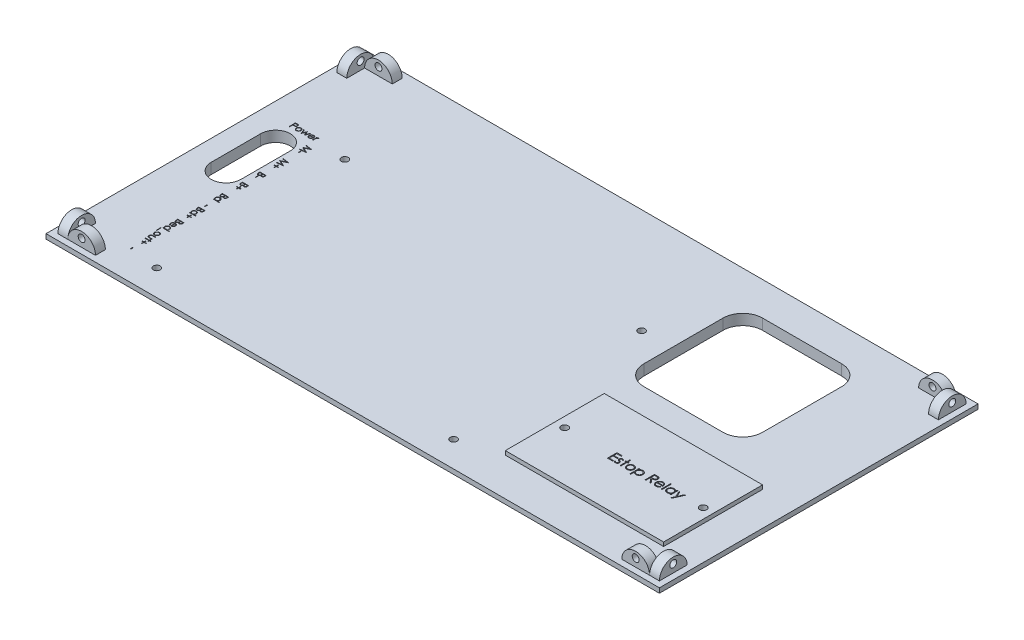
SolidWorks part; units mm, degrees
ref_plane "Front Plane" through (0, 0, 0) normal (0, 0, 1) x (1, 0, 0)
ref_plane "Top Plane" through (0, 0, 0) normal (0, 1, 0) x (1, 0, 0)
ref_plane "Right Plane" through (0, 0, 0) normal (1, 0, 0) x (0, 0, -1)
sketch "Sketch1" plane through (0, 0, 0) normal (0, 1, 0) x (1, 0, 0)
  line L1 (-111.0644, -68.8857) -> (48.9356, -68.8857) construction
  line L2 (-111.0644, -68.8857) -> (-111.0644, 26.1143) construction
  line L3 (-111.0644, 26.1143) -> (48.9356, 26.1143) construction
  line L4 (48.9356, -68.8857) -> (48.9356, 26.1143) construction
  line L5 (-151.0644, 76.1143) -> (152.9356, 76.1143) construction
  line L6 (152.9356, -78.8857) -> (152.9356, 76.1143) construction
  line L10 (-154.0644, 79.1143) -> (155.9356, 79.1143)
  line L11 (155.9356, -81.8857) -> (155.9356, 79.1143)
  line L12 (-154.0644, -81.8857) -> (155.9356, -81.8857)
  line L13 (-154.0644, -81.8857) -> (-154.0644, 79.1143)
  line L14 (-151.0644, -78.8857) -> (152.9356, -78.8857) construction
  line L15 (-151.0644, -78.8857) -> (-151.0644, 76.1143) construction
  line L17 (113.9356, 62.2405) -> (53.9356, 62.2405)
  line L18 (113.9356, 62.2405) -> (113.9356, 2.2405)
  line L19 (113.9356, 2.2405) -> (53.9356, 2.2405)
  line L20 (53.9356, 62.2405) -> (53.9356, 2.2405)
  line L21 (0.9356, 76.1143) -> (0.9356, -78.8857) construction
  line L22 (-151.0644, -1.3857) -> (152.9356, -1.3857) construction
  circle A0 centre (-111.0644, 26.1143) radius 1.75
  circle A1 centre (38.9356, 26.1143) radius 1.75
  circle A2 centre (38.9356, -68.8857) radius 1.75
  circle A3 centre (-111.0644, -68.8857) radius 1.75
  dimension "D6" = 3.5
  dimension "D1" = 95
  dimension "D2" = 160
  dimension "D4" = 40
  dimension "D5" = 10
  dimension "D9" = 161
  dimension "D10" = 310
  dimension "D11" = 60
  dimension "D12" = 165
  dimension "D3" = 3
  dimension "D7" = 2
  dimension "D8" = 2
extrude "Base" add sketch "Sketch1" against normal blind 5.4
ref_plane "Plane1" through (-151.0644, 0, 0) normal (1, 0, 0) x (0, 0, -1)
sketch "Sketch3" plane through (-151.0644, 0, 0) normal (1, 0, 0) x (0, 0, -1)
  line L1 (-78.8857, 0) -> (76.1143, 0) construction
  line L2 (76.1143, 0) -> (69.1143, 0) construction
  line L3 (62.1143, 0) -> (76.1143, 0)
  line L4 (-78.8857, 0) -> (-64.8857, 0)
  line L5 (-71.8857, 7) -> (-71.8857, 0) construction
  line L6 (69.1143, 7) -> (69.1143, 0) construction
  line L7 (-78.8857, 0) -> (76.1143, 0) construction
  arc A0 (76.1143, 0) -> (62.1143, 0) centre (69.1143, 0) ccw
  arc A1 (-64.8857, 0) -> (-78.8857, 0) centre (-71.8857, 0) ccw
  circle A2 centre (-71.8857, 4) radius 1.75
  circle A3 centre (69.1143, 4) radius 1.75
  point P18 (79.1143, 0)
  dimension "D1" = 14
  dimension "D2" = 3.5
  dimension "D4" = 3.5
  dimension "D3" = 3
  dimension "D5" = 4
  dimension "D6" = 14
extrude "Long_Side_connectors" add sketch "Sketch3" along normal blind 5
ref_plane "Plane2" through (0, 0, 78.8857) normal (0, 0, 1) x (1, 0, 0)
sketch "Sketch4" plane through (0, 0, 78.8857) normal (0, 0, 1) x (1, 0, 0)
  line L1 (-146.0644, 0) -> (-132.0644, 0)
  line L2 (-146.0644, 0) -> (-132.0644, 0)
  line L3 (-139.0644, 7) -> (-139.0644, 0) construction
  arc A0 (-132.0644, 0) -> (-146.0644, 0) centre (-139.0644, 0) ccw
  circle A1 centre (-139.0644, 4) radius 1.75
  dimension "D1" = 14
  dimension "D2" = 4
extrude "Short_side_connectors" add sketch "Sketch4" against normal blind 5 contours A0 L3 A1 L2 | L3 A0 L1 A1 region at (-142.3536, 2.8239, 78.8857) region at (-135.7752, 2.8239, 78.8857)
ref_plane "Plane6" through (0, 0, 1.3857) normal (0, 0, 1) x (1, 0, 0)
mirror "Mirror1" about plane through (0, 0, 1.3857) normal (0, 0, 1) of "Short_side_connectors"
ref_plane "Plane5" through (0.9356, 0, 0) normal (1, 0, 0) x (0, 0, -1)
mirror "Mirror3" about plane through (0.9356, 0, 0) normal (1, 0, 0) of "Long_Side_connectors", "Mirror1"
sketch "Sketch6" plane through (0, 0, 0) normal (0, 1, 0) x (1, 0, 0)
  line L0 (48.9356, -68.8857) -> (48.9356, 26.1143) construction
  line L1 (58.9356, -62.7595) -> (138.9356, -62.7595)
  line L2 (58.9356, -62.7595) -> (58.9356, -12.7595)
  line L3 (58.9356, -12.7595) -> (138.9356, -12.7595)
  line L4 (138.9356, -62.7595) -> (138.9356, -12.7595)
  line L5 (58.9356, -62.7595) -> (138.9356, -12.7595) construction
  line L6 (58.9356, -12.7595) -> (138.9356, -62.7595) construction
  line L7 (113.9356, 2.2405) -> (53.9356, 2.2405) construction
  point P0 (98.9356, -37.7595)
  point P9 (83.9356, 2.2405)
  dimension "D1" = 50
  dimension "D2" = 80
  dimension "D3" = 10
  dimension "D4" = 15
extrude "Estop_relay" add sketch "Sketch6" along normal blind 2 contours L3 L4 L1 L2
sketch "Sketch8" plane through (0, 2, 0) normal (0, 1, 0) x (1, 0, 0)
  line L0 (58.9356, -37.7595) -> (138.9356, -37.7595) construction
  line L1 (58.9356, -62.7595) -> (58.9356, -12.7595) construction
  line L2 (138.9356, -62.7595) -> (138.9356, -12.7595) construction
  line L3 (58.9356, -37.7595) -> (63.9356, -37.7595) construction
  line L4 (98.9356, -12.7595) -> (98.9356, -62.7595) construction
  line L5 (58.9356, -12.7595) -> (138.9356, -12.7595) construction
  line L6 (58.9356, -62.7595) -> (138.9356, -62.7595) construction
  circle A0 centre (63.9356, -37.7595) radius 1.77
  circle A1 centre (133.9356, -37.7595) radius 1.77
  dimension "D2" = 3.54
  dimension "D1" = 5
extrude "Estop_bolts" cut sketch "Sketch8" against normal blind 5.3
sketch "Sketch9" plane through (0, 0, 0) normal (0, 1, 0) x (1, 0, 0)
  line L0 (-136.0644, 16.1143) -> (-136.0644, -8.8857) construction
  line L1 (-128.5644, 16.1143) -> (-128.5644, -8.8857)
  line L2 (-143.5644, 16.1143) -> (-143.5644, -8.8857)
  line L3 (-151.0644, 76.1143) -> (152.9356, 76.1143) construction
  line L4 (-151.0644, -78.8857) -> (-151.0644, 76.1143) construction
  arc A0 (-128.5644, 16.1143) -> (-143.5644, 16.1143) centre (-136.0644, 16.1143) ccw
  arc A1 (-143.5644, -8.8857) -> (-128.5644, -8.8857) centre (-136.0644, -8.8857) ccw
  point P2 (-136.0644, 3.6143)
  dimension "D1" = 25
  dimension "D2" = 15
  dimension "D3" = 60
  dimension "D4" = 15
extrude "Cut-Extrude4" cut sketch "Sketch9" against normal up to next contours A0 L2 A1 L1
sketch "Sketch10" plane through (0, 0, 0) normal (0, 1, 0) x (1, 0, 0)
  line L0 (-126.8751, 25.1928) -> (-127.2079, -70.1564) construction
  line L1 (-128.5644, 16.1143) -> (-128.5644, -8.8857) construction
  text T0 "Power"
  text T1 "  M-     M+    B-    B+    Bd   - Bd+  Bed_out+   -\r\n"
  text T2 "Estop Relay" font "Century Gothic" height in points 18
  dimension "D1" = 0.2
extrude "Text" cut sketch "Sketch10" against normal blind 1 and the other way through all
sketch "Sketch11" plane through (0, 0, 0) normal (0, 1, 0) x (1, 0, 0)
  line L0 (-146.0644, -73.8857) -> (-132.0644, -73.8857) construction
  line L1 (-141.0644, -68.8857) -> (-136.0644, -68.8857) construction
  line L2 (-141.0644, -68.8857) -> (-141.0644, -63.8857) construction
  line L3 (-141.0644, -63.8857) -> (-136.0644, -63.8857) construction
  line L4 (-136.0644, -68.8857) -> (-136.0644, -63.8857) construction
  line L5 (-146.0644, -73.8857) -> (-146.0644, -64.8857) construction
  line L6 (-146.0644, 71.1143) -> (-132.0644, 71.1143) construction
  line L7 (-141.0644, 66.1143) -> (-136.0644, 66.1143) construction
  line L8 (-141.0644, 66.1143) -> (-141.0644, 61.1143) construction
  line L9 (-141.0644, 61.1143) -> (-136.0644, 61.1143) construction
  line L10 (-136.0644, 66.1143) -> (-136.0644, 61.1143) construction
  line L11 (-146.0644, 62.1143) -> (-146.0644, 71.1143) construction
  line L12 (0.9356, -85.25) -> (0.9356, 85.25) construction
  circle A0 centre (-141.0644, -63.8857) radius 1.75
  circle A1 centre (-136.0644, -68.8857) radius 1.75
  circle A2 centre (-141.0644, 61.1143) radius 1.75
  circle A3 centre (-136.0644, 66.1143) radius 1.75
  circle A4 centre (142.9356, -63.8857) radius 1.75
  circle A5 centre (137.9356, -68.8857) radius 1.75
  circle A6 centre (142.9356, 61.1143) radius 1.75
  circle A7 centre (137.9356, 66.1143) radius 1.75
  dimension "D3" = 3.5
  dimension "D4" = 3.5
  dimension "D8" = 5
  dimension "D1" = 5
  dimension "D2" = 5
  dimension "D5" = 5
  dimension "D6" = 5
  dimension "4" = 5
  dimension "D7" = 5
  dimension "D9" = 5
extrude "Cut-Extrude6" cut sketch "Sketch11" along normal blind 3.5 from surface starting at face at (-111.0644, -5.4, 70.6357)
chamfer "Chamfer2" distance 3 angle 45 4 edges at (155.9356, -5.4, 1.3857) (0.9356, -5.4, -79.1143) (-154.0644, -5.4, 1.3857) (0.9356, -5.4, 81.8857)
fillet "Fillet1" radius 10 4 edges at (113.9356, -2.7, -2.2405) (53.9356, -2.7, -2.2405) (113.9356, -2.7, -62.2405) (53.9356, -2.7, -62.2405)
